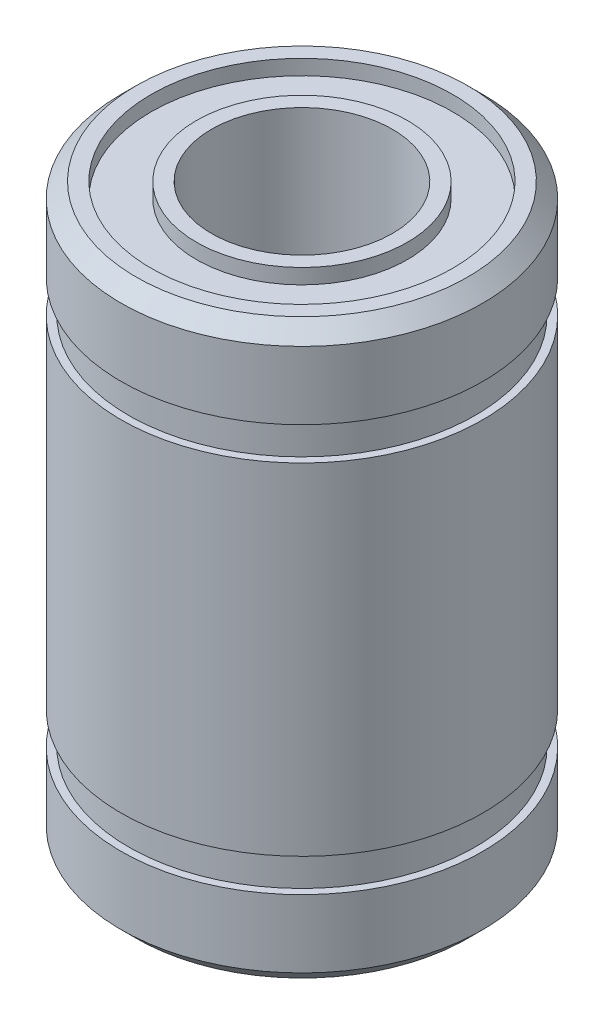
SolidWorks part; units mm, degrees
ref_plane "Front Plane" through (0, 0, 0) normal (0, 0, 1) x (1, 0, 0)
ref_plane "Top Plane" through (0, 0, 0) normal (0, 1, 0) x (1, 0, 0)
ref_plane "Right Plane" through (0, 0, 0) normal (1, 0, 0) x (0, 0, -1)
sketch "Sketch1" plane through (0, 0, 0) normal (0, 0, 1) x (1, 0, 0)
  line L0 (0, 9.5) -> (0, 0) construction
  line L1 (0, 0) -> (0, -9.5) construction
  line L2 (0, 9.5) -> (3, 9.5) construction
  line L3 (0, -9.5) -> (3, -9.5) construction
  line L4 (3, -9.5) -> (3, 9.5)
  line L5 (3, 9.5) -> (5.5, 9.5)
  line L6 (5.5, 9.5) -> (6, 9)
  line L7 (6, 9) -> (6, 6.75)
  line L8 (6, 5.65) -> (6, 6.75) construction
  line L9 (6, -6.75) -> (6, -5.65) construction
  line L10 (6, 5.65) -> (6, -5.65)
  line L11 (6, -9) -> (5.5, -9) construction
  line L12 (5.5, -9) -> (5.5, -9.5) construction
  line L13 (6, -6.75) -> (6, -9)
  line L14 (6, -9) -> (5.5, -9.5)
  line L15 (5.5, -9.5) -> (3, -9.5)
  line L16 (6, 9) -> (5.5, 9) construction
  line L17 (5.5, 9) -> (5.5, 9.5) construction
  line L18 (5.5, -9) -> (5.5, 9) construction
  line L19 (6.48, -6.2) -> (6.48, 6.2) construction
  line L20 (5.75, -6.2) -> (6.48, -6.2) construction
  line L21 (6, 6.75) -> (5.75, 6.75)
  line L22 (0, 0) -> (6, 0) construction
  line L23 (5.75, 6.75) -> (5.75, 5.65)
  line L24 (5.75, 5.65) -> (6, 5.65)
  line L25 (6, -5.65) -> (5.75, -5.65)
  line L26 (5.75, -5.65) -> (5.75, -6.75)
  line L27 (5.75, -6.75) -> (6, -6.75)
  arc A0 (6, 6.75) -> (6, 5.65) centre (6.48, 6.2) ccw construction
  arc A1 (6, -5.65) -> (6, -6.75) centre (6.48, -6.2) ccw construction
  dimension "Total_length" = 19
  dimension "Inside_diameter" = 6
  dimension "D4" = 0.5
  dimension "Distance_between_lockingrings" = 13.5
  dimension "Diameter_outside" = 12
  dimension "Locking_ring_width" = 1.1
  dimension "Locking_ring_groove_dia" = 11.5
revolve "Revolve1" add sketch "Sketch1" angle 360 about L0
sketch "Sketch2" plane through (0, 9.5, 0) normal (0, 1, 0) x (1, 0, 0)
  circle A0 centre (0, 0) radius 3.5
  circle A1 centre (0, 0) radius 5
  circle A2 centre (0, 0) radius 6 construction
  circle A3 centre (0, 0) radius 3 construction
  dimension "D1" = 1
  dimension "D2" = 0.5
extrude "Cut-Extrude1" cut sketch "Sketch2" against normal blind 0.5
mirror "Mirror1" about plane through (0, 0, 0) normal (0, 1, 0) of "Cut-Extrude1"
sketch "Sketch3"
  dimension "D1" = 0.4
split line "Split Line1"
